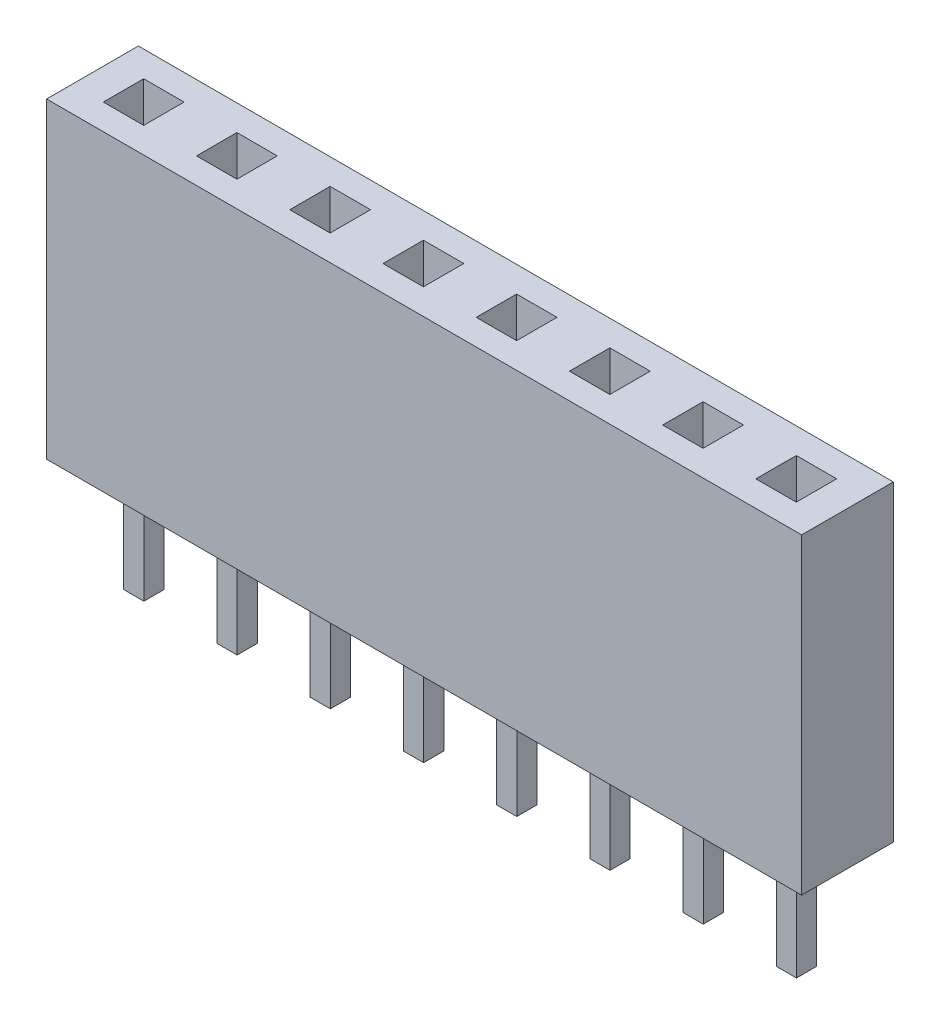
SolidWorks part; units mm, degrees
ref_plane "Front Plane" through (0, 0, 0) normal (0, 0, 1) x (1, 0, 0)
ref_plane "Top Plane" through (0, 0, 0) normal (0, 1, 0) x (1, 0, 0)
ref_plane "Right Plane" through (0, 0, 0) normal (1, 0, 0) x (0, 0, -1)
sketch "Sketch1" plane through (0, 0, 0) normal (0, 0, 1) x (1, 0, 0)
  line L1 (0, 0) -> (20.57, 0)
  line L2 (0, 0) -> (0, 8.5)
  line L3 (0, 8.5) -> (20.57, 8.5)
  line L4 (20.57, 0) -> (20.57, 8.5)
  dimension "D1" = 8.5
  dimension "D2" = 20.57
extrude "Boss-Extrude1" add sketch "Sketch1" along normal mid plane 2.5
sketch "Sketch2" plane through (0, 0, 0) normal (0, -1, 0) x (1, 0, 0)
  line L0 (0, 0) -> (20.57, 0) construction
  line L1 (20.57, 1.25) -> (20.57, -1.25) construction
  line L2 (3.385, -0.55) -> (4.485, -0.55)
  line L3 (0.845, -0.55) -> (1.945, -0.55)
  line L4 (0.845, -0.55) -> (0.845, 0.55)
  line L5 (0.845, 0.55) -> (1.945, 0.55)
  line L6 (1.945, -0.55) -> (1.945, 0.55)
  line L7 (0.845, -0.55) -> (1.945, 0.55) construction
  line L8 (0.845, 0.55) -> (1.945, -0.55) construction
  line L9 (3.385, -0.55) -> (3.385, 0.55)
  line L10 (3.385, 0.55) -> (4.485, 0.55)
  line L11 (4.485, -0.55) -> (4.485, 0.55)
  line L12 (3.385, -0.55) -> (4.485, 0.55) construction
  line L13 (3.385, 0.55) -> (4.485, -0.55) construction
  line L14 (5.925, -0.55) -> (7.025, -0.55)
  line L15 (5.925, -0.55) -> (5.925, 0.55)
  line L16 (5.925, 0.55) -> (7.025, 0.55)
  line L17 (7.025, -0.55) -> (7.025, 0.55)
  line L18 (5.925, -0.55) -> (7.025, 0.55) construction
  line L19 (5.925, 0.55) -> (7.025, -0.55) construction
  line L20 (8.465, -0.55) -> (9.565, -0.55)
  line L21 (8.465, -0.55) -> (8.465, 0.55)
  line L22 (8.465, 0.55) -> (9.565, 0.55)
  line L23 (9.565, -0.55) -> (9.565, 0.55)
  line L24 (8.465, -0.55) -> (9.565, 0.55) construction
  line L25 (8.465, 0.55) -> (9.565, -0.55) construction
  line L26 (11.005, -0.55) -> (12.105, -0.55)
  line L27 (11.005, -0.55) -> (11.005, 0.55)
  line L28 (11.005, 0.55) -> (12.105, 0.55)
  line L29 (12.105, -0.55) -> (12.105, 0.55)
  line L30 (11.005, -0.55) -> (12.105, 0.55) construction
  line L31 (11.005, 0.55) -> (12.105, -0.55) construction
  line L32 (13.545, -0.55) -> (14.645, -0.55)
  line L33 (13.545, -0.55) -> (13.545, 0.55)
  line L34 (13.545, 0.55) -> (14.645, 0.55)
  line L35 (14.645, -0.55) -> (14.645, 0.55)
  line L36 (13.545, -0.55) -> (14.645, 0.55) construction
  line L37 (13.545, 0.55) -> (14.645, -0.55) construction
  line L38 (16.085, -0.55) -> (17.185, -0.55)
  line L39 (16.085, -0.55) -> (16.085, 0.55)
  line L40 (16.085, 0.55) -> (17.185, 0.55)
  line L41 (17.185, -0.55) -> (17.185, 0.55)
  line L42 (16.085, -0.55) -> (17.185, 0.55) construction
  line L43 (16.085, 0.55) -> (17.185, -0.55) construction
  line L44 (18.625, -0.55) -> (19.725, -0.55)
  line L45 (18.625, -0.55) -> (18.625, 0.55)
  line L46 (18.625, 0.55) -> (19.725, 0.55)
  line L47 (19.725, -0.55) -> (19.725, 0.55)
  line L48 (18.625, -0.55) -> (19.725, 0.55) construction
  line L49 (18.625, 0.55) -> (19.725, -0.55) construction
  line L78 (1.395, 0) -> (3.935, 0) construction
  point P5 (1.395, 0)
  point P12 (3.935, 0)
  point P17 (6.475, 0)
  point P22 (9.015, 0)
  point P27 (11.555, 0)
  point P32 (14.095, 0)
  point P37 (16.635, 0)
  point P42 (19.175, 0)
  dimension "D1" = 1.1
  dimension "D3" = 1.395
  dimension "D4" = 2.54
  dimension "D2" = 8
extrude "Cut-Extrude1" cut sketch "Sketch2" against normal through all contours L3 L6 L5 L4 | L2 L11 L10 L9 | L14 L17 L16 L15 | L20 L23 L22 L21 | L26 L29 L28 L27 | L32 L35 L34 L33 | L38 L41 L40 L39 | L44 L47 L46 L45 region at (3.935, 0, 0) region at (1.395, 0, 0) region at (6.475, 0, 0) region at (9.015, 0, 0) region at (11.555, 0, 0) region at (14.095, 0, 0) region at (16.635, 0, 0) region at (19.175, 0, 0)
sketch "Sketch3" plane through (0, 0, 0) normal (0, -1, 0) x (1, 0, 0)
  line L1 (0, 1.25) -> (20.57, 1.25)
  line L2 (0, 1.25) -> (0, -1.25)
  line L3 (0, -1.25) -> (20.57, -1.25)
  line L4 (20.57, 1.25) -> (20.57, -1.25)
extrude "Boss-Extrude2" add sketch "Sketch3" against normal blind 1
sketch "Sketch4" plane through (0, 0, 0) normal (0, -1, 0) x (1, 0, 0)
  line L0 (1.125, 0) -> (1.675, 0) construction
  line L1 (1.125, 0.275) -> (1.675, 0.275)
  line L2 (1.125, 0.275) -> (1.125, -0.275)
  line L3 (1.125, -0.275) -> (1.675, -0.275)
  line L4 (1.675, 0.275) -> (1.675, -0.275)
  line L5 (0, 0) -> (20.57, 0) construction
  line L6 (20.57, 1.25) -> (20.57, -1.25) construction
  line L7 (0, 1.25) -> (0, -1.25) construction
  line L8 (3.665, 0.275) -> (3.665, -0.275)
  line L9 (3.665, 0.275) -> (4.215, 0.275)
  line L10 (3.665, -0.275) -> (4.215, -0.275)
  line L11 (4.215, 0.275) -> (4.215, -0.275)
  line L12 (6.205, 0.275) -> (6.205, -0.275)
  line L13 (6.205, 0.275) -> (6.755, 0.275)
  line L14 (6.205, -0.275) -> (6.755, -0.275)
  line L15 (6.755, 0.275) -> (6.755, -0.275)
  line L16 (8.745, 0.275) -> (8.745, -0.275)
  line L17 (8.745, 0.275) -> (9.295, 0.275)
  line L18 (8.745, -0.275) -> (9.295, -0.275)
  line L19 (9.295, 0.275) -> (9.295, -0.275)
  line L20 (11.285, 0.275) -> (11.285, -0.275)
  line L21 (11.285, 0.275) -> (11.835, 0.275)
  line L22 (11.285, -0.275) -> (11.835, -0.275)
  line L23 (11.835, 0.275) -> (11.835, -0.275)
  line L24 (13.825, 0.275) -> (13.825, -0.275)
  line L25 (13.825, 0.275) -> (14.375, 0.275)
  line L26 (13.825, -0.275) -> (14.375, -0.275)
  line L27 (14.375, 0.275) -> (14.375, -0.275)
  line L28 (16.365, 0.275) -> (16.365, -0.275)
  line L29 (16.365, 0.275) -> (16.915, 0.275)
  line L30 (16.365, -0.275) -> (16.915, -0.275)
  line L31 (16.915, 0.275) -> (16.915, -0.275)
  line L32 (18.905, 0.275) -> (18.905, -0.275)
  line L33 (18.905, 0.275) -> (19.455, 0.275)
  line L34 (18.905, -0.275) -> (19.455, -0.275)
  line L35 (19.455, 0.275) -> (19.455, -0.275)
  line L52 (1.125, 0.275) -> (3.665, 0.275) construction
  point P6 (1.4, 0)
  dimension "D1" = 0.55
  dimension "D2" = 1.4
  dimension "D4" = 2.54
  dimension "D3" = 8
extrude "Boss-Extrude3" add sketch "Sketch4" along normal blind 3 separate body
ref_axis "Axis1" through (1.395, 0, 0) along (0, -1, 0)
ref_axis "Axis2" through (19.175, 0, 0) along (0, -1, 0)
